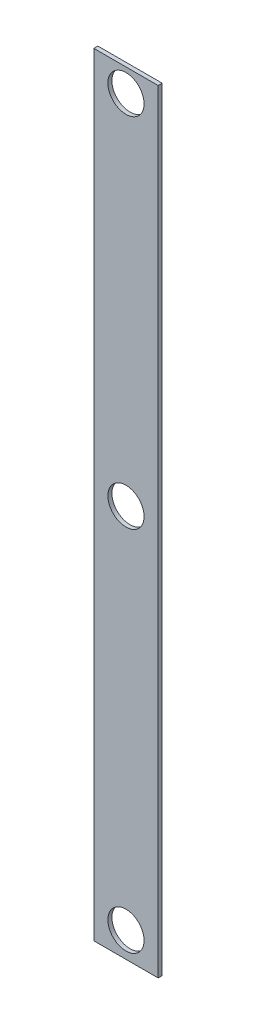
SolidWorks part; units mm, degrees
ref_plane "Front Plane" through (0, 0, 0) normal (0, 0, 1) x (1, 0, 0)
ref_plane "Top Plane" through (0, 0, 0) normal (0, 1, 0) x (1, 0, 0)
ref_plane "Right Plane" through (0, 0, 0) normal (1, 0, 0) x (0, 0, -1)
sketch "Sketch1" plane through (0, 0, 0) normal (0, 0, 1) x (1, 0, 0)
  line L1 (0, 0) -> (50.8, 0)
  line L2 (0, 0) -> (0, -609.6)
  line L3 (0, -609.6) -> (50.8, -609.6)
  line L4 (50.8, 0) -> (50.8, -609.6)
  dimension "D1" = 609.6
  dimension "D2" = 50.8
extrude "Boss-Extrude1" add sketch "Sketch1" along normal blind 3.175
sketch "Sketch2" plane through (0, 0, 3.175) normal (0, 0, 1) x (1, 0, 0)
  line L0 (50.8, 0) -> (0, 0) construction
  line L1 (25.4, 0) -> (25.4, -609.6) construction
  line L2 (0, -609.6) -> (50.8, -609.6) construction
  line L3 (0, -609.6) -> (50.8, -609.6) construction
  circle A0 centre (25.4, -18.1414) radius 14.279
  circle A1 centre (25.4, -589.6) radius 14.279
  circle A2 centre (25.4, -300) radius 14.279
  point P9 (25.4, -609.6)
  dimension "D1" = 28.558
  dimension "D2" = 28.558
  dimension "D4" = 28.558
  dimension "D5" = 300
  dimension "D3" = 20
extrude "Cut-Extrude1" cut sketch "Sketch2" against normal through all
